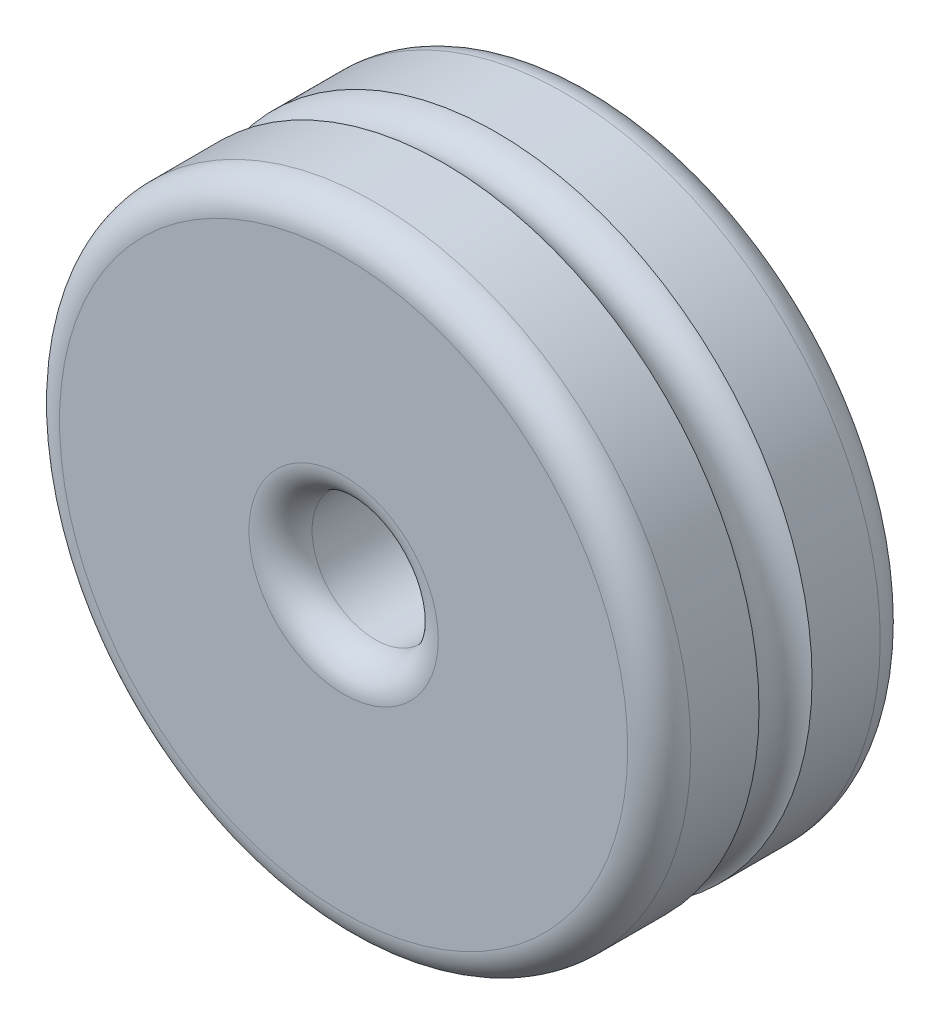
SolidWorks part; units mm, degrees
ref_plane "Front Plane" through (0, 0, 0) normal (0, 0, 1) x (1, 0, 0)
ref_plane "Top Plane" through (0, 0, 0) normal (0, 1, 0) x (1, 0, 0)
ref_plane "Right Plane" through (0, 0, 0) normal (1, 0, 0) x (0, 0, -1)
sketch "Sketch1" plane through (0, 0, 0) normal (0, 0, 1) x (1, 0, 0)
  circle A0 centre (0, 0) radius 10
  circle A1 centre (0, 0) radius 50
  dimension "D1" = 20
extrude "Boss-Extrude1" add sketch "Sketch1" along normal blind 20 and the other way blind 20
fillet "Fillet1" radius 5 4 edges at (10, 0, -20) (10, 0, 20) (50, 0, 20) (50, 0, -20)
sketch "Sketch3" plane through (0, 0, 0) normal (0, 1, 0) x (1, 0, 0)
  line L0 (0, 9.9304) -> (0, -11.8638) construction
  circle A0 centre (-51.6715, 0) radius 4.5209
  point P5 (-53.7906, 0)
  point P6 (-51.6715, 0)
revolve "Cut-Revolve1" cut sketch "Sketch3" angle 360 about L0
